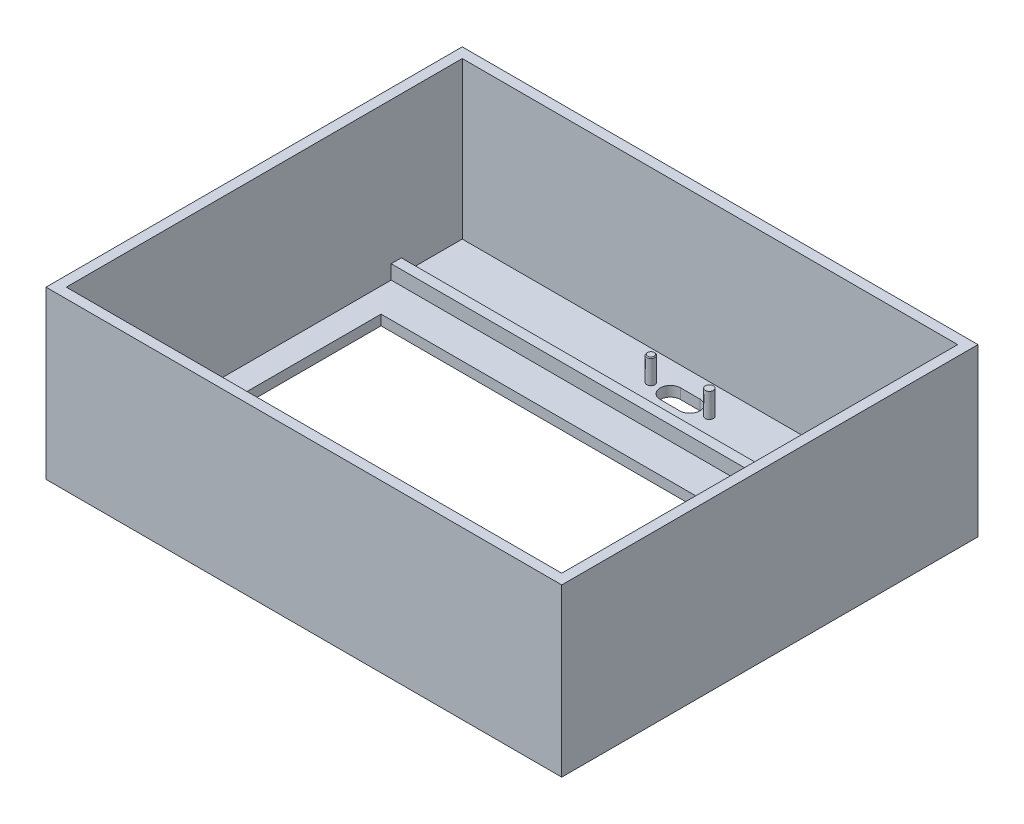
SolidWorks part; units mm, degrees
ref_plane "Front Plane" through (0, 0, 0) normal (0, 0, 1) x (1, 0, 0)
ref_plane "Top Plane" through (0, 0, 0) normal (0, 1, 0) x (1, 0, 0)
ref_plane "Right Plane" through (0, 0, 0) normal (1, 0, 0) x (0, 0, -1)
sketch "Sketch1" plane through (0, 0, 0) normal (0, 1, 0) x (1, 0, 0)
  line L1 (0, 0) -> (127, 0)
  line L2 (0, 0) -> (0, 85)
  line L3 (0, 85) -> (127, 85)
  line L4 (127, 0) -> (127, 85)
extrude "Boss-Extrude1" add sketch "Sketch1" along normal blind 2.5
sketch "Sketch2" plane through (0, 2.5, 0) normal (0, 1, 0) x (1, 0, 0)
  line L0 (0, 85) -> (127, 85)
  line L1 (127, 85) -> (127, 0)
  line L2 (127, 0) -> (0, 0)
  line L3 (0, 0) -> (0, 85)
  line L5 (2.5, 82.5) -> (124.5, 82.5)
  line L6 (2.5, 82.5) -> (2.5, 2.5)
  line L7 (2.5, 2.5) -> (124.5, 2.5)
  line L8 (124.5, 82.5) -> (124.5, 2.5)
  dimension "D1" = 2.5
  dimension "D2" = 2.5
  dimension "D3" = 2.5
  dimension "D4" = 2.5
extrude "Boss-Extrude2" add sketch "Sketch2" along normal blind 38.5
sketch "Sketch3" plane through (0, 0, 0) normal (0, -1, 0) x (-1, 0, 0)
  line L0 (-127, 85) -> (0, 85) construction
  line L1 (-8.5, 5.5) -> (-118.5, 5.5)
  line L2 (-8.5, 5.5) -> (-8.5, 74)
  line L3 (-8.5, 74) -> (-118.5, 74)
  line L4 (-118.5, 5.5) -> (-118.5, 74)
  line L6 (0, 0) -> (-127, 0) construction
  line L7 (-127, 0) -> (-127, 85) construction
  line L8 (0, 85) -> (0, 0) construction
  dimension "D1" = 11
  dimension "D2" = 5.5
  dimension "D3" = 8.5
  dimension "D4" = 8.5
extrude "Cut-Extrude1" cut sketch "Sketch3" against normal blind 2.5
sketch "Sketch6" plane through (0, 0, 0) normal (0, -1, 0) x (-1, 0, 0)
  line L8 (-61.1, 92.6537) -> (-65.9, 92.6537) construction
  line L9 (-61.1, 90.1537) -> (-65.9, 90.1537)
  line L10 (-61.1, 95.1537) -> (-65.9, 95.1537)
  arc A0 (-61.1, 90.1537) -> (-61.1, 95.1537) centre (-61.1, 92.6537) ccw
  arc A2 (-65.9, 95.1537) -> (-65.9, 90.1537) centre (-65.9, 92.6537) ccw
  point P1 (-63.5, 92.6537)
sketch "Sketch9" plane through (0, 0, -85) normal (0, 0, -1) x (-1, 0, 0)
  line L0 (-127, 0) -> (0, 0) construction
  line L1 (-127, 0) -> (0, 0)
  line L2 (-127, 0) -> (-127, 2.5)
  line L4 (0, 0) -> (0, 2.5)
  line L5 (-127, 41) -> (-127, 0) construction
  line L6 (0, 41) -> (0, 0) construction
  line L7 (-2.5, 2.5) -> (-124.5, 2.5)
  line L8 (-127, 41) -> (-124.5, 41)
  line L9 (-127, 41) -> (-127, 2.5)
  line L11 (-124.5, 41) -> (-124.5, 2.5)
  line L12 (0, 41) -> (-2.5, 41)
  line L13 (0, 41) -> (0, 2.5)
  line L15 (-2.5, 41) -> (-2.5, 2.5)
  dimension "D2" = 2.5
  dimension "D3" = 2.5
extrude "Boss-Extrude3" add sketch "Sketch9" along normal blind 15
sketch "Sketch10" plane through (0, 41, 0) normal (0, 1, 0) x (1, 0, 0)
  line L1 (2.5, 85) -> (124.5, 85)
  line L2 (2.5, 85) -> (2.5, 82.5)
  line L3 (2.5, 82.5) -> (124.5, 82.5)
  line L4 (124.5, 85) -> (124.5, 82.5)
extrude "Cut-Extrude2" cut sketch "Sketch10" against normal blind 35
sketch "Sketch11" plane through (0, 0, -100) normal (0, 0, -1) x (-1, 0, 0)
  line L1 (0, 0) -> (-127, 0)
  line L2 (0, 0) -> (0, 41)
  line L3 (0, 41) -> (-127, 41)
  line L4 (-127, 0) -> (-127, 41)
extrude "Boss-Extrude4" add sketch "Sketch11" along normal blind 2.5
sketch "Sketch13" plane through (0, 2.5, 0) normal (0, 1, 0) x (1, 0, 0)
  circle A0 centre (56.3, 92.6537) radius 1
  circle A1 centre (70.7, 92.6537) radius 1
  arc A2 (61.1, 95.1537) -> (61.1, 90.1537) centre (61.1, 92.6537) ccw construction
  dimension "D1" = 14.4
  dimension "D2" = 4.8
  dimension "D3" = 4.8
extrude "Cut-Extrude4" cut sketch "Sketch6" against normal blind 2.5
sketch "Sketch14" plane through (0, 2.5, 0) normal (0, 1, 0) x (1, 0, 0)
  line L1 (56, 87.1537) -> (71, 87.1537)
  line L2 (56, 87.1537) -> (56, 86.1537)
  line L3 (56, 86.1537) -> (71, 86.1537)
  line L4 (71, 87.1537) -> (71, 86.1537)
  arc A0 (61.1, 95.1537) -> (61.1, 90.1537) centre (61.1, 92.6537) ccw construction
  arc A1 (65.9, 90.1537) -> (65.9, 95.1537) centre (65.9, 92.6537) ccw construction
  dimension "D1" = 5.1
  dimension "D2" = 5.1
extrude "Cut-Extrude5" cut sketch "Sketch14" against normal blind 1.5
extrude "Boss-Extrude6" add sketch "Sketch13" along normal blind 6
chamfer "Chamfer1" distance 0.2 angle 45 1 edges at (55.3, 8.5, -92.6537)
sketch "Sketch15" plane through (0, 8.5, 0) normal (0, 1, 0) x (1, 0, 0)
  circle A0 centre (56.3, 92.6537) radius 1 construction
  circle A1 centre (56.3, 92.6537) radius 1
ref_axis "Axis1" through (56.3, 10.1761, -92.6537) along (0, -1, 0)
curve "Helix/Spiral1" parameters "D10001"=5.5, "D30001"=2, "D40001"=0.4, "D10002"=0.5, "D30002"=4, "D40002"=0.4, "D50000"=0.4
sketch "Sketch19" plane through (0, 0, 0) normal (-1, 0, 0) x (0, 0, 1)
  line L3 (-93.4637, 8.5) -> (-95.4138, 7.3741)
  line L4 (-95.4138, 7.3741) -> (-95.4138, 9.6259)
  line L5 (-95.4138, 9.6259) -> (-93.4637, 8.5)
  line L6 (-102.5, 0) -> (0, 0) construction
  line L7 (-102.5, 0) -> (-102.5, 41) construction
  point P2 (0, 0)
  dimension "D1" = 60
  dimension "D2" = 8.5
  dimension "D3" = 9.0363
